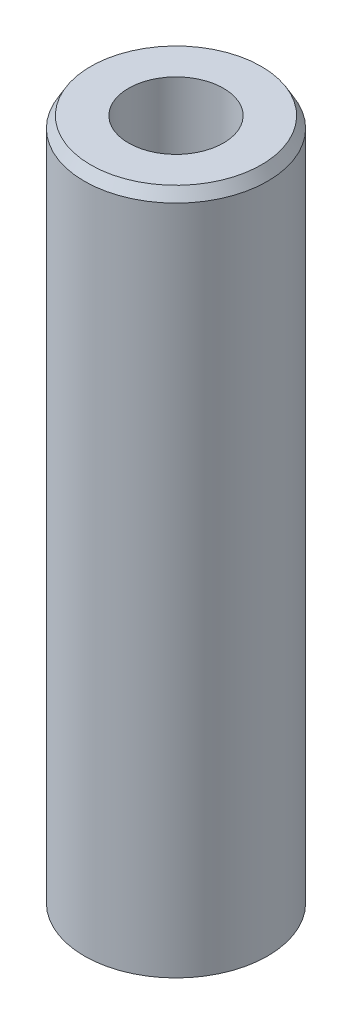
SolidWorks part; units mm, degrees
ref_plane "Front Plane" through (0, 0, 0) normal (0, 0, 1) x (1, 0, 0)
ref_plane "Top Plane" through (0, 0, 0) normal (0, 1, 0) x (1, 0, 0)
ref_plane "Right Plane" through (0, 0, 0) normal (1, 0, 0) x (0, 0, -1)
sketch "Sketch1" plane through (0, 0, 0) normal (0, 1, 0) x (1, 0, 0)
  circle A0 centre (0, 0) radius 50
  dimension "SHAFT_OD" = 100
extrude "Boss-Extrude1" add sketch "Sketch1" along normal blind 375.4566
sketch "Sketch2" plane through (0, 0, 0) normal (0, 1, 0) x (1, 0, 0)
  circle A0 centre (0, 0) radius 25.9027
  dimension "BORE_D" = 51.8055
extrude "Cut-Extrude1" cut sketch "Sketch2" along normal through all
chamfer "Chamfer1" distance 5.9857 angle 30 2 edges at (0, 375.4566, 50) (0, 0, 50) first distance on face at (0, 375.4566, 50) first distance on face at (0, 0, 25.9027)
